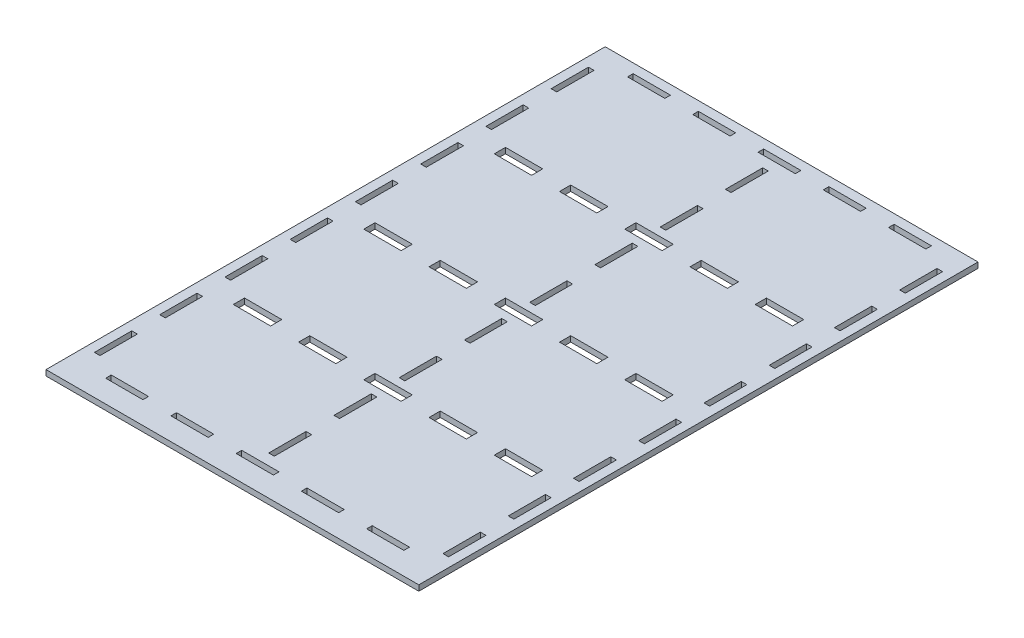
SolidWorks part; units mm, degrees
ref_plane "Front Plane" through (0, 0, 0) normal (0, 0, 1) x (1, 0, 0)
ref_plane "Top Plane" through (0, 0, 0) normal (0, 1, 0) x (1, 0, 0)
ref_plane "Right Plane" through (0, 0, 0) normal (1, 0, 0) x (0, 0, -1)
sketch "Sketch1" plane through (0, 0, 0) normal (0, 1, 0) x (1, 0, 0)
  line L1 (0, 0) -> (200, 0)
  line L2 (0, 0) -> (0, 300)
  line L3 (0, 300) -> (200, 300)
  line L4 (200, 0) -> (200, 300)
  line L5 (0, 0) -> (200, 300) construction
  line L6 (0, 300) -> (200, 0) construction
  line L7 (20, 295) -> (40, 295)
  line L8 (20, 295) -> (20, 292)
  line L9 (20, 292) -> (40, 292)
  line L10 (40, 295) -> (40, 292)
  line L11 (20, 295) -> (40, 292) construction
  line L12 (20, 292) -> (40, 295) construction
  line L13 (5, 286) -> (8, 286)
  line L14 (5, 286) -> (5, 266)
  line L15 (5, 266) -> (8, 266)
  line L16 (8, 286) -> (8, 266)
  line L17 (5, 286) -> (8, 266) construction
  line L18 (5, 266) -> (8, 286) construction
  line L38 (0, 150) -> (200, 150) construction
  line L39 (100, 300) -> (100, 0) construction
  point P10 (30, 293.5)
  point P15 (6.5, 276)
  dimension "D1" = 300
  dimension "D2" = 200
  dimension "D3" = 3
  dimension "D4" = 20
  dimension "D5" = 5
  dimension "D6" = 5
  dimension "D7" = 14
  dimension "D8" = 20
extrude "Boss-Extrude1" add sketch "Sketch1" along normal blind 3 contours L1 L4 L3 L2 L7 L10 L9 L8 L13 L16 L15 L14 | L10 L7 L8 L9 | L16 L13 L14 L15 region at (100.1638, 0, -149.73) region at (30, 0, -293.5) region at (6.5, 0, -276)
sketch "Sketch2" plane through (0, 3, 0) normal (0, 1, 0) x (1, 0, 0)
  line L0 (5, 266) -> (8, 266) construction
  line L1 (8, 286) -> (8, 266) construction
  line L2 (5, 286) -> (5, 266) construction
  line L3 (5, 286) -> (8, 286) construction
  line L4 (8, 286) -> (5, 286)
  line L5 (8, 266) -> (8, 286)
  line L6 (5, 266) -> (8, 266)
  line L7 (5, 286) -> (5, 266)
  line L8 (8, 286) -> (5, 286)
  line L9 (8, 266) -> (8, 286)
  line L10 (5, 266) -> (8, 266)
  line L11 (5, 286) -> (5, 266)
  line L12 (40, 295) -> (20, 295)
  line L13 (40, 292) -> (40, 295)
  line L14 (20, 292) -> (40, 292)
  line L15 (20, 295) -> (20, 292)
  line L16 (40, 295) -> (20, 295)
  line L17 (40, 292) -> (40, 295)
  line L18 (20, 292) -> (40, 292)
  line L19 (20, 295) -> (20, 292)
  line L20 (0, 0) -> (200, 0)
  line L21 (200, 0) -> (200, 300)
  line L22 (200, 300) -> (0, 300)
  line L23 (0, 300) -> (0, 0)
  line L24 (0, 0) -> (200, 0)
  line L25 (200, 0) -> (200, 300)
  line L26 (200, 300) -> (0, 300)
  line L27 (0, 300) -> (0, 0)
  line L28 (20, 295) -> (20, 292) construction
  line L29 (40, 295) -> (40, 292) construction
  line L30 (20, 292) -> (40, 292) construction
  line L31 (20, 295) -> (40, 295) construction
  line L32 (5, 266) -> (8, 266)
  line L33 (8, 286) -> (8, 266)
  line L34 (5, 286) -> (5, 266)
  line L35 (5, 286) -> (8, 286)
  line L36 (20, 295) -> (20, 292)
  line L37 (40, 295) -> (40, 292)
  line L38 (20, 292) -> (40, 292)
  line L39 (20, 295) -> (40, 295)
  dimension "D1" = 0
  dimension "D2" = 0
  dimension "D3" = 0
extrude "Cut-Extrude2" cut sketch "Sketch2" against normal blind 10 contours L16 L19 L18 L17 | L8 L11 L10 L9 region at (6.5, 3, -276) region at (30, 3, -293.5)
pattern_linear "LPattern3" count 5 spacing 35 along (1, 0, 0) count 5 spacing 70 along (0, 0, 1) of face at (30, 1.5, -292) of face at (20, 1.5, -293.5) of face at (30, 1.5, -295) of face at (40, 1.5, -293.5)
pattern_linear "LPattern4" count 3 spacing 93.5 along (1, 0, 0) count 8 spacing 35 along (0, 0, 1) of face at (5, 1.5, -276) of face at (8, 1.5, -276) of face at (6.5, 1.5, -286) of face at (6.5, 1.5, -266)
sketch "Sketch4" plane through (0, 3, 0) normal (0, 1, 0) x (1, 0, 0)
  line L0 (20, 222) -> (40, 222) construction
  line L1 (6.5, 293.5) -> (100, 293.5)
  line L2 (6.5, 293.5) -> (6.5, 223.5)
  line L3 (6.5, 223.5) -> (100, 223.5)
  line L4 (100, 293.5) -> (100, 223.5)
  line L5 (20, 15) -> (20, 12) construction
  line L6 (5, 231) -> (8, 231) construction
  line L7 (100, 300) -> (100, 0) construction
  line L8 (40, 222) -> (40, 225) construction
  line L9 (6.5, 223.5) -> (100, 223.5)
  line L10 (6.5, 223.5) -> (6.5, 153.5)
  line L11 (6.5, 153.5) -> (100, 153.5)
  line L12 (100, 223.5) -> (100, 153.5)
  line L13 (20, 225) -> (20, 222) construction
  line L14 (40, 225) -> (20, 225) construction
  line L15 (6.5, 153.5) -> (100, 153.5)
  line L16 (6.5, 153.5) -> (6.5, 83.5)
  line L17 (6.5, 83.5) -> (100, 83.5)
  line L18 (100, 153.5) -> (100, 83.5)
  line L19 (20, 222) -> (40, 222)
  line L20 (40, 222) -> (40, 225)
  line L21 (6.5, 83.5) -> (100, 83.5)
  line L22 (6.5, 83.5) -> (6.5, 13.5)
  line L23 (6.5, 13.5) -> (100, 13.5)
  line L24 (100, 83.5) -> (100, 13.5)
  line L25 (20, 225) -> (20, 222)
  line L26 (40, 225) -> (20, 225)
  line L28 (20, 226.5) -> (40, 226.5)
  line L29 (20, 226.5) -> (20, 220.5)
  line L30 (20, 220.5) -> (40, 220.5)
  line L31 (40, 226.5) -> (40, 220.5)
  point P18 (20, 13.5)
  point P27 (30, 220.9155)
  point P28 (20, 223.5)
  dimension "D1" = 7.5
  dimension "D2" = 6
extrude "Cut-Extrude3" cut sketch "Sketch4" against normal blind 10 contours L28 L31 L30 L29
pattern_linear "LPattern5" count 5 spacing 35 along (1, 0, 0) count 3 spacing 70 along (0, 0, 1) of "Cut-Extrude3"
